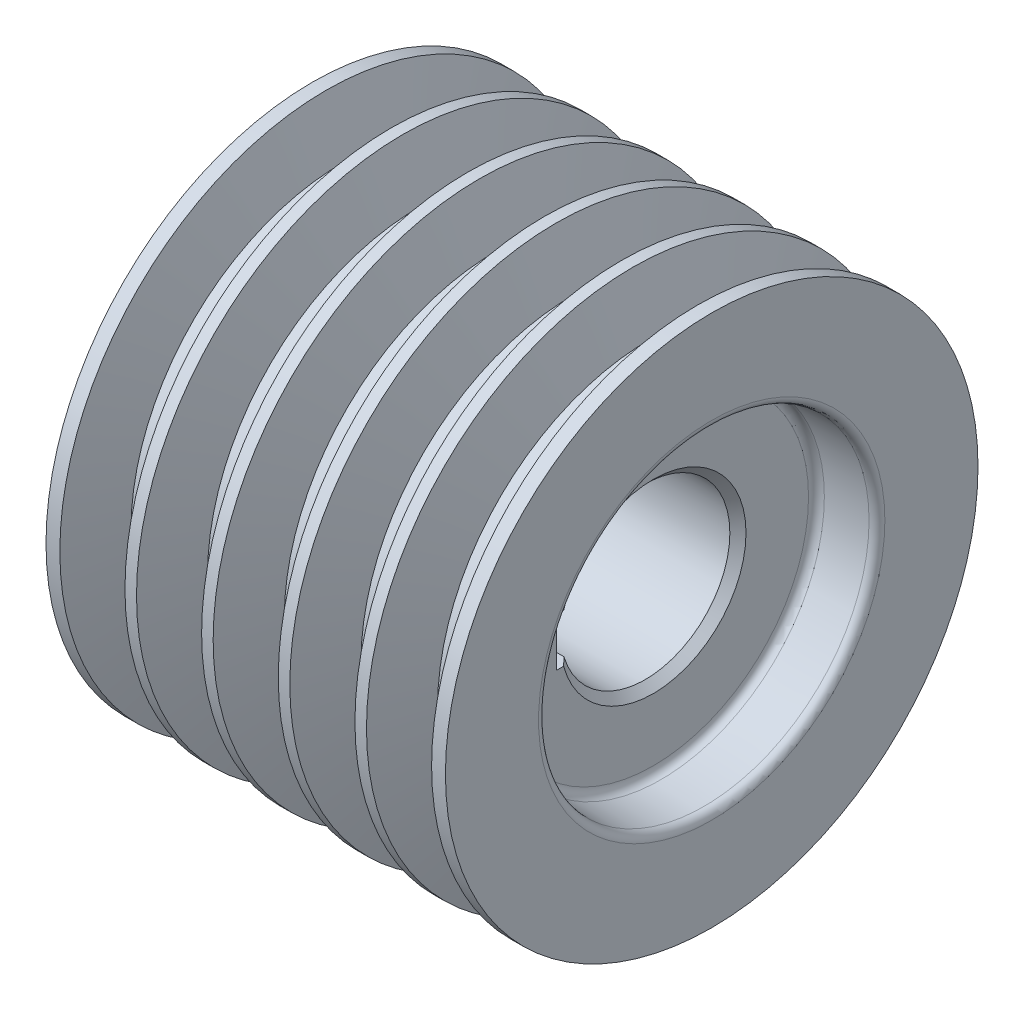
SolidWorks part; units mm, degrees
ref_plane "前视基准面" through (0, 0, 0) normal (0, 0, 1) x (1, 0, 0)
ref_plane "上视基准面" through (0, 0, 0) normal (0, 1, 0) x (1, 0, 0)
ref_plane "右视基准面" through (0, 0, 0) normal (1, 0, 0) x (0, 0, -1)
sketch "草图1" plane through (0, 0, 0) normal (0, 0, 1) x (1, 0, 0)
  line L1 (-19.0478, 45.1088) -> (79.9522, 45.1088)
  line L2 (-19.0478, 45.1088) -> (-19.0478, -20.8912)
  line L3 (-19.0478, -20.8912) -> (79.9522, -20.8912)
  line L4 (79.9522, 45.1088) -> (79.9522, -20.8912)
  line L5 (30.4522, 53.0742) -> (30.4522, -28.8566) construction
  line L6 (-19.0478, 45.1088) -> (79.9522, -20.8912) construction
  line L7 (-19.0478, -20.8912) -> (79.9522, 45.1088) construction
  point P0 (30.4522, 12.1088)
  dimension "D1" = 99
  dimension "D2" = 66
revolve "旋转1" add sketch "草图1" angle 360 about L3 region at (30.4522, 12.1088, 0)
sketch "草图2" plane through (-19.0478, 0, 0) normal (-1, 0, 0) x (0, 0, 1)
  circle A0 centre (0, -20.8912) radius 41
extrude "切除-拉伸1" cut sketch "草图2" against normal blind 14.5 draft 2.29
ref_plane "基准面1" through (30.4522, 0, 0) normal (-1, 0, 0) x (0, 0, 1)
mirror "镜向1" about plane through (30.4522, 0, 0) normal (-1, 0, 0) of "切除-拉伸1"
fillet "圆角1" radius 2 4 edges at (-4.5478, -20.8912, 40.4202) (-19.0478, -20.8912, 41) (65.4522, -20.8912, -40.4202) (79.9522, -20.8912, 41)
sketch "草图3" plane through (0, 0, 0) normal (0, 0, 1) x (1, 0, 0)
  line L0 (64.5095, 31.6088) -> (72.3949, 31.6088)
  line L1 (-19.0478, -20.8912) -> (79.9522, -20.8912) construction
  line L2 (-19.0478, 45.1088) -> (-19.0478, -86.8912) construction
  line L3 (79.9522, -86.8912) -> (79.9522, 45.1088) construction
  line L5 (79.9522, 45.1088) -> (-19.0478, 45.1088) construction
  line L6 (76.5223, 45.1088) -> (72.3949, 31.6088)
  line L7 (64.5095, 31.6088) -> (60.3822, 45.1088)
  line L8 (60.3822, 45.1088) -> (76.5223, 45.1088)
ref_plane "基准面2" through (72.3949, 31.6088, 0) normal (1, 0, 0) x (0, 0, -1)
sketch "草图4" plane through (72.3949, 31.6088, 0) normal (1, 0, 0) x (0, 0, -1)
  circle A0 centre (0, -52.5) radius 52.5
sweep "切除-扫描1" cut profiles "草图3" path "草图4"
ref_axis "基准轴1" through (60.3822, -20.8912, 0) along (-1, 0, 0)
pattern_linear "阵列(线性)1" count 3 spacing 19 along (-1, 0, 0) of "切除-扫描1"
pattern_linear "阵列(线性)2" count 2 spacing 57 along (-1, 0, 0) of "切除-扫描1"
pattern_linear "阵列(线性)3" count 2 spacing 76 along (-1, 0, 0) of "切除-扫描1"
sketch "草图5" plane through (-4.5478, 0, 0) normal (-1, 0, 0) x (0, 0, 1)
  circle A0 centre (0, -20.8912) radius 21
extrude "切除-拉伸2" cut sketch "草图5" against normal through all
chamfer "倒角1" distance 2 angle 45 2 edges at (65.4522, -20.8912, -21) (-4.5478, -20.8912, 21)
sketch "草图6" plane through (65.4522, 0, 0) normal (1, 0, 0) x (0, 0, -1)
  line L0 (23, -20.8912) -> (-23, -20.8912)
  line L1 (0, -14.8912) -> (-24, -14.8912)
  line L2 (0, -14.8912) -> (0, -26.8912)
  line L3 (0, -26.8912) -> (-24, -26.8912)
  line L4 (-24, -14.8912) -> (-24, -26.8912)
  circle A0 centre (0, -20.8912) radius 23 construction
  circle M1 centre (0, -20.8912) radius 23
  dimension "D1" = 24
  dimension "D2" = 6
  dimension "D3" = 6
extrude "切除-拉伸3" cut sketch "草图6" against normal through all contours L3 L2 L0 M1 | L2 L1 L0 M1 | L1 L4 L3 M1 region at (65.4522, -23.8737, 11.3694) region at (65.4522, -17.9086, 11.3694) region at (65.4522, -20.8912, 23.346)
